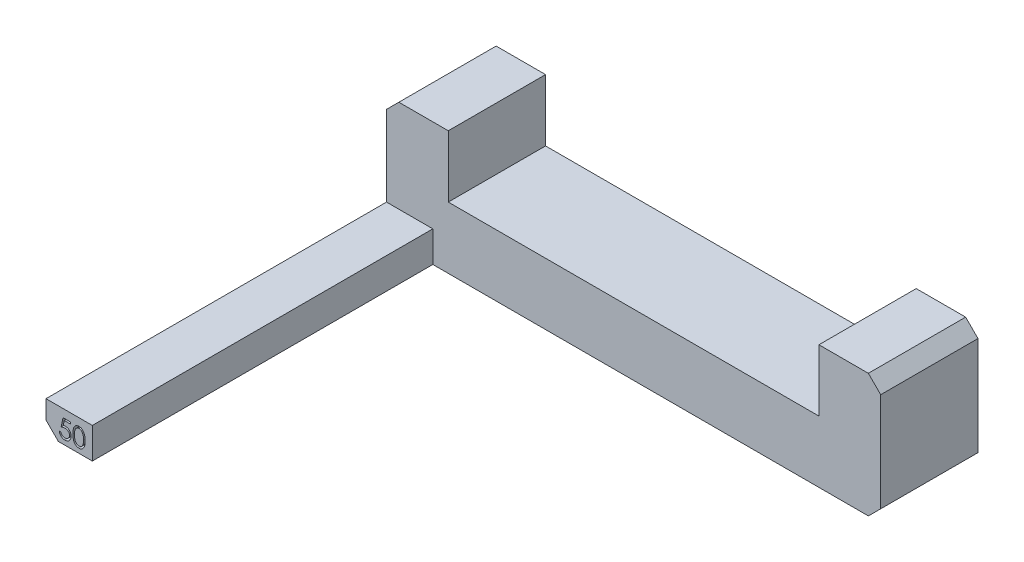
SolidWorks part; units mm, degrees
ref_plane "Front Plane" through (0, 0, 0) normal (0, 0, 1) x (1, 0, 0)
ref_plane "Top Plane" through (0, 0, 0) normal (0, 1, 0) x (1, 0, 0)
ref_plane "Right Plane" through (0, 0, 0) normal (1, 0, 0) x (0, 0, -1)
sketch "Sketch1" plane through (0, 0, 0) normal (0, 0, 1) x (1, 0, 0)
  line L1 (0, 0) -> (-101.6, 0)
  line L2 (0, 0) -> (0, 25.4)
  line L3 (0, 25.4) -> (-101.6, 25.4)
  line L4 (-101.6, 0) -> (-101.6, 25.4)
  line L5 (-12.7, 25.4) -> (-88.9, 25.4)
  line L6 (-12.7, 25.4) -> (-12.7, 12.7)
  line L7 (-12.7, 12.7) -> (-88.9, 12.7)
  line L8 (-88.9, 25.4) -> (-88.9, 12.7)
  point P9 (-50.8, 25.4)
  point P10 (-50.8, 12.7)
  dimension "D1" = 101.6
  dimension "D2" = 25.4
  dimension "D3" = 12.7
  dimension "D4" = 12.7
extrude "Boss-Extrude1" add sketch "Sketch1" along normal blind 20 contours L8 L3 L4 L1 L2 L6 L7 region at (-50.8, 8.89, 0)
sketch "Sketch2" plane through (0, 0, 20) normal (0, 0, 1) x (1, 0, 0)
  line L1 (-101.6, 0) -> (-92.075, 0)
  line L2 (-101.6, 0) -> (-101.6, 6.35)
  line L3 (-101.6, 6.35) -> (-92.075, 6.35)
  line L4 (-92.075, 0) -> (-92.075, 6.35)
  dimension "D1" = 9.525
  dimension "D2" = 6.35
extrude "Boss-Extrude2" add sketch "Sketch2" along normal blind 70
sketch "Sketch3" plane through (0, 0, 90) normal (0, 0, 1) x (1, 0, 0)
  line L0 (-101.6, 0) -> (-92.075, 0) construction
  line L1 (-101.6, 6.35) -> (-101.6, 0) construction
  text T0 "50" font "Century Gothic" height in points 14
  dimension "D1" = 1.016
  dimension "D2" = 2.54
extrude "Cut-Extrude1" cut sketch "Sketch3" against normal blind 2
chamfer "Chamfer1" distance 2.54 angle 45 4 edges at (0, 0, 10) (-101.6, 0, 45) (0, 25.4, 10) (-101.6, 25.4, 10)
